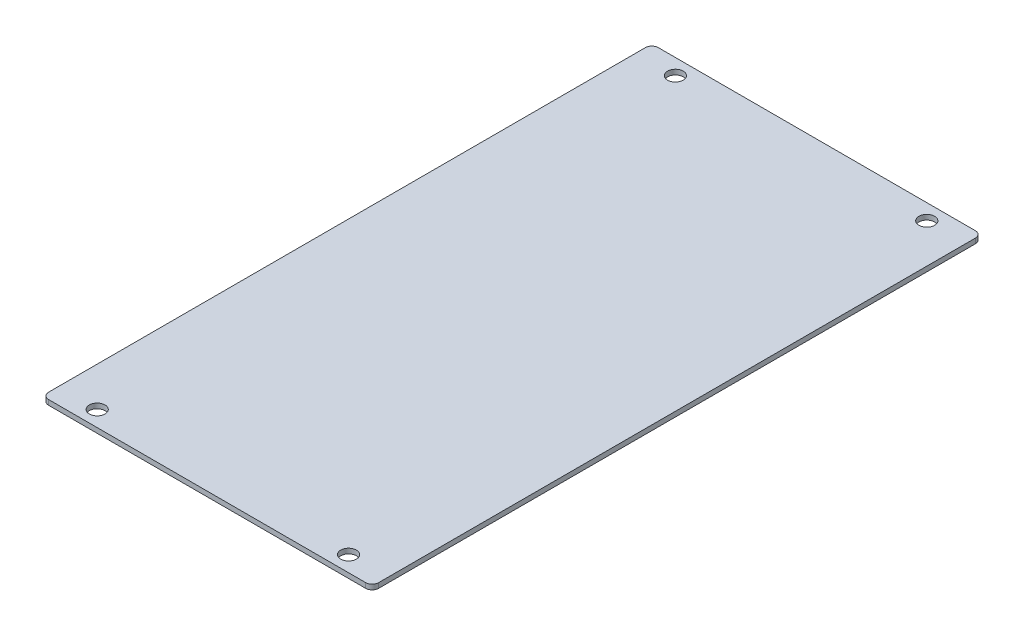
SolidWorks part; units mm, degrees
note: The reader was unsure of these and kept them because the rebuilt part matched: thickness of "Base-Flange1", "Sheet-Metal1", "Sheet-Metal2".
material "3003 Alloy"
ref_plane "Front Plane" through (0, 0, 0) normal (0, 0, 1) x (1, 0, 0)
ref_plane "Top Plane" through (0, 0, 0) normal (0, 1, 0) x (1, 0, 0)
ref_plane "Right Plane" through (0, 0, 0) normal (1, 0, 0) x (0, 0, -1)
sketch "Sketch1" plane through (0, 0, 0) normal (0, 1, 0) x (1, 0, 0)
  line L1 (0, 0) -> (210, 0)
  line L2 (0, 0) -> (0, 388)
  line L3 (0, 388) -> (210, 388)
  line L4 (210, 0) -> (210, 388)
  dimension "D1" = 388
  dimension "D2" = 210
base flange "Base-Flange1" sketch "Sketch1" thickness 3.175 reverse thickness direction no parameters "D1"=0.7366
fillet "Fillet1" radius 4.1 4 edges at (0, -1.5875, 0) (0, -1.5875, -388) (210, -1.5875, -388) (210, -1.5875, 0)
sketch "Sketch6" plane through (0, 0, 0) normal (0, 1, 0) x (1, 0, 0)
  line L0 (0, 0) -> (210, 0) construction
  line L2 (0, 0) -> (0, 388) construction
  line L3 (210, 0) -> (210, 388) construction
  line L4 (0, 388) -> (210, 388) construction
  circle A0 centre (25, 378) radius 5
  circle A1 centre (185, 378) radius 5
  circle A2 centre (185, 10) radius 5
  circle A3 centre (25, 10) radius 5
  dimension "D2" = 10
  dimension "D3" = 10
  dimension "D4" = 10
  dimension "D5" = 10
  dimension "D1" = 25
  dimension "D6" = 25
  dimension "D7" = 25
  dimension "D8" = 25
  dimension "D9" = 10
  dimension "D10" = 0
  dimension "D11" = 10
  dimension "D12" = 0
extrude "Cut-Extrude1" cut sketch "Sketch6" against normal blind 10 normal cut yes
sketch "Bend-Lines1" [suppressed] plane through (0, 0, 0) normal (0, 1, 0) x (1, 0, 0)
sketch "Bounding-Box1" [suppressed] plane through (0, 0, 0) normal (0, 1, 0) x (1, 0, 0)
sheet metal parameters "Sheet-Metal1" thickness 3.175 parameters "D1"=0.7366
flat pattern "Flat-Pattern1" [suppressed]
sketch "Bend-Lines2" plane through (0, 0, 0) normal (0, 1, 0) x (1, 0, 0)
sketch3d "Bounding-Box2" [suppressed]
  line L0 (210.0002, 0.0002, 0) -> (210, 248, 0) construction
  line L1 (0.0002, 0, 0) -> (0, 247.9998, 0) construction
  line L2 (210.0002, 0.0002, 0) -> (0.0002, 0, 0) construction
  line L3 (210, 248, 0) -> (0, 247.9998, 0) construction
sheet metal parameters "Sheet-Metal2" thickness 3.175 parameters "D1"=0.7366, "D7"=4.1
flat pattern "Flat-Pattern1"
sketch "Bend-Lines2" plane through (0, 0, 0) normal (0, 1, 0) x (1, 0, 0)
sketch3d "Bounding-Box2" [suppressed]
  line L0 (210.0003, 0.0002, 0) -> (210, 388, 0) construction
  line L1 (0.0003, 0, 0) -> (0, 387.9998, 0) construction
  line L2 (210.0003, 0.0002, 0) -> (0.0003, 0, 0) construction
  line L3 (210, 388, 0) -> (0, 387.9998, 0) construction
